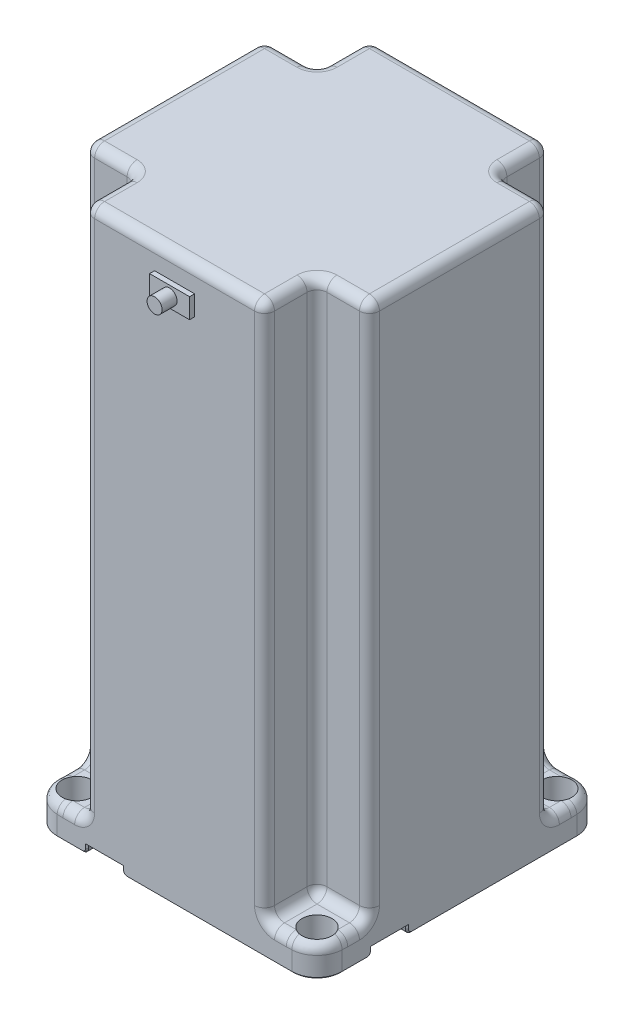
SolidWorks part; units mm, degrees
ref_plane "Płaszczyzna przednia" through (0, 0, 0) normal (0, 0, 1) x (1, 0, 0)
ref_plane "Płaszczyzna górna" through (0, 0, 0) normal (0, 1, 0) x (1, 0, 0)
ref_plane "Płaszczyzna prawa" through (0, 0, 0) normal (1, 0, 0) x (0, 0, -1)
sketch "Szkic1" plane through (0, 0, 0) normal (0, 1, 0) x (1, 0, 0)
  line L1 (28.5, -28.5) -> (-28.5, -28.5)
  line L2 (28.5, -28.5) -> (28.5, 28.5)
  line L3 (28.5, 28.5) -> (-28.5, 28.5)
  line L4 (-28.5, -28.5) -> (-28.5, 28.5)
  line L5 (28.5, -28.5) -> (-28.5, 28.5) construction
  line L6 (28.5, 28.5) -> (-28.5, -28.5) construction
  point P0 (0, 0)
  dimension "D1" = 57
  dimension "D2" = 57
extrude "Dodanie-wyciągnięcie1" add sketch "Szkic1" along normal blind 113
fillet "Zaokrąglenie1" radius 5 4 edges at (-28.5, 56.5, 28.5) (-28.5, 56.5, -28.5) (28.5, 56.5, -28.5) (28.5, 56.5, 28.5)
sketch "Szkic2" plane through (0, 113, 0) normal (0, 1, 0) x (1, 0, 0)
  line L0 (0, -31.35) -> (0, 31.35) construction
  line L1 (-30, -30) -> (30, -30)
  line L2 (-30, -30) -> (-30, 30)
  line L3 (-30, 30) -> (30, 30)
  line L6 (30, -30) -> (30, 30)
  line L7 (-30, -30) -> (30, 30) construction
  line L8 (-30, 30) -> (30, -30) construction
  line L9 (-31.35, 0) -> (31.35, 0) construction
  circle A0 centre (24, 24) radius 3
  circle A1 centre (24, -24) radius 3
  circle A2 centre (-24, -24) radius 3
  circle A4 centre (-24, 24) radius 3
  point P0 (0, 0)
  dimension "D2" = 6
  dimension "D1" = 60
  dimension "D3" = 60
  dimension "D4" = 6
  dimension "D5" = 6
extrude "Wytnij-wyciągnięcie1" cut sketch "Szkic2" against normal blind 113 contours A2 | A4 | A1 | A0 region at (-24, 113, 24)
sketch "Szkic3" plane through (0, 113, 0) normal (0, 1, 0) x (1, 0, 0)
  line L1 (-29.0454, 18) -> (-18, 18)
  line L2 (-29.0454, 18) -> (-29.0454, 29.0454)
  line L3 (-29.0454, 29.0454) -> (-18, 29.0454)
  line L4 (-18, 18) -> (-18, 29.0454)
  line L5 (-29.0454, 18) -> (-18, 29.0454) construction
  line L6 (-29.0454, 29.0454) -> (-18, 18) construction
  line L7 (0, -31.35) -> (0, 31.35) construction
  line L8 (29.0454, 29.0454) -> (18, 29.0454)
  line L9 (18, 18) -> (18, 29.0454)
  line L10 (29.0454, 18) -> (18, 18)
  line L11 (29.0454, 18) -> (29.0454, 29.0454)
  line L12 (-31.35, 0) -> (31.35, 0) construction
  line L13 (29.0454, -18) -> (29.0454, -29.0454)
  line L14 (29.0454, -18) -> (18, -18)
  line L15 (18, -18) -> (18, -29.0454)
  line L16 (29.0454, -29.0454) -> (18, -29.0454)
  line L17 (-29.0454, -29.0454) -> (-18, -29.0454)
  line L18 (-18, -18) -> (-18, -29.0454)
  line L19 (-29.0454, -18) -> (-18, -18)
  line L20 (-29.0454, -18) -> (-29.0454, -29.0454)
  circle A0 centre (-24, 24) radius 3 construction
  point P0 (-24, 24)
  dimension "D1" = 6
  dimension "D2" = 6
  dimension "D3" = 11.0454
extrude "Wytnij-wyciągnięcie2" cut sketch "Szkic3" against normal blind 107
fillet "Zaokrąglenie2" radius 2 41 edges at (-28.5, 6, -20.75) (-20.75, 6, -28.5) (28.5, 6, -20.75) (20.75, 6, -28.5) (28.5, 6, 20.75) (20.75, 6, 28.5) (-18, 59.5, 28.5) (-28.5, 6, 20.75) (-28.5, 113, 0) (0, 113, -28.5) (28.5, 113, 0) (0, 113, 28.5) (-18, 113, 23.25) (-28.5, 59.5, -18) (-23.25, 6, -18) (-23.25, 113, -18) (-18, 59.5, -18) (-18, 6, -23.25) (-18, 59.5, -28.5) (-18, 113, -23.25) (28.5, 59.5, -18) (23.25, 113, -18) (23.25, 6, -18) (18, 59.5, -28.5) (18, 6, -23.25) (18, 59.5, -18) (18, 113, -23.25) (28.5, 59.5, 18) (23.25, 6, 18) (23.25, 113, 18) (18, 59.5, 18) (18, 6, 23.25) (18, 59.5, 28.5) (18, 113, 23.25) (-28.5, 59.5, 18) (-23.25, 113, 18) (-18, 59.5, 18) (-23.25, 6, 18) (-18, 6, 23.25) (-20.75, 6, 28.5) (-27.0355, 6, 27.0355)
sketch "Szkic5" plane through (0, 0, 0) normal (0, -1, 0) x (1, 0, 0)
  circle A0 centre (0, 0) radius 19
  dimension "D1" = 38
extrude "Dodanie-wyciągnięcie2" add sketch "Szkic5" along normal blind 0.9
fillet "Zaokrąglenie8" radius 1 1 edges at (0, -0.9, -19)
sketch "Szkic6" plane through (0, -0.9, 0) normal (0, -1, 0) x (-1, 0, 0)
  circle A0 centre (0, 0) radius 5
  dimension "D1" = 10
extrude "Wytnij-wyciągnięcie4" cut sketch "Szkic6" against normal blind 50
sketch "Szkic7" plane through (0, 0, 0) normal (0, -1, 0) x (1, 0, 0)
  line L0 (-23.5, 28.5) -> (23.5, 28.5) construction
  circle A0 centre (-14, 23.5) radius 2
  circle A1 centre (23.5, 14) radius 2
  circle A2 centre (14, -23.5) radius 2
  circle A3 centre (-23.5, -14) radius 2
  circle A4 centre (0, 0) radius 5 construction
  circle A6 centre (-24, 24) radius 3 construction
  point P15 (0, 0)
  dimension "D1" = 4
  dimension "D2" = 10
  dimension "D4" = 5
  dimension "D3" = 4
extrude "Wytnij-wyciągnięcie5" cut sketch "Szkic7" against normal blind 100
sketch "Szkic8" plane through (0, 0, 0) normal (0, -1, 0) x (1, 0, 0)
  line L0 (-17.5, 23.5) -> (-17.5, 28.5)
  line L1 (-23.5, 28.5) -> (23.5, 28.5) construction
  line L2 (-17.5, 28.5) -> (-10.5, 28.5)
  line L3 (-10.5, 28.5) -> (-10.5, 23.5)
  line L4 (-28.5, -23.5) -> (-28.5, 23.5) construction
  arc A0 (-17.5, 23.5) -> (-10.5, 23.5) centre (-14, 23.5) ccw
  point P3 (-14, 28.5)
  dimension "D1" = 3.5
  dimension "D2" = 14.5
  dimension "D3" = 5
extrude "Wytnij-wyciągnięcie6" cut sketch "Szkic8" against normal blind 1.5
fillet "Zaokrąglenie9" radius 1 3 edges at (-17.5, 0, 26) (-10.5, 0, 26) (-14, 0, 20)
pattern_circular "Szyk kołowy3" count 4 over 360 about axis through (0, 49.1, 0) along (0, -1, 0) of "Wytnij-wyciągnięcie6", "Zaokrąglenie9" reverse direction yes
chamfer "Sfazowanie1" distance 0.3 angle 45 36 edges at (-23.5, 1.5, -16) (14, 1.5, -25.5) (23.5, 1.5, 12) (-14, 1.5, 21.5) (-28.5, 1.5, -14) (-14, 1.5, 28.5) (28.5, 1.5, 14) (28.5, 1.25, 10.5) (28.5, 0.2929, 10.2071) (28.5, 0, -7) (17.5, 1.25, -28.5) (27.0355, 0, -27.0355) (17.7929, 0.2929, -28.5) (21, 0, -28.5) (14, 1.5, -28.5) (-28.5, 1.25, -17.5) (-28.5, 0.2929, -17.7929) (10.5, 1.25, -28.5) (-28.5, 0, -21) (10.2071, 0.2929, -28.5) (-27.0355, 0, -27.0355) (-7, 0, -28.5) (-28.5, 1.25, -10.5) (-28.5, 0.2929, -10.2071) (-28.5, 0, 7) (-17.5, 1.25, 28.5) (-27.0355, 0, 27.0355) (-17.7929, 0.2929, 28.5) (-21, 0, 28.5) (28.5, 1.25, 17.5) (28.5, 0.2929, 17.7929) (-10.5, 1.25, 28.5) (28.5, 0, 21) (-10.2071, 0.2929, 28.5) (27.0355, 0, 27.0355) (7, 0, 28.5)
sketch "Szkic9" plane through (0, 0, 28.5) normal (0, 0, 1) x (1, 0, 0)
  line L0 (-16, 113) -> (16, 113) construction
  line L1 (4, 104) -> (-4, 104)
  line L2 (4, 104) -> (4, 108)
  line L3 (4, 108) -> (-4, 108)
  line L4 (-4, 104) -> (-4, 108)
  line L5 (4, 104) -> (-4, 108) construction
  line L6 (4, 108) -> (-4, 104) construction
  line L7 (16, 111) -> (-16, 111) construction
  point P0 (0, 106)
  point P10 (0, 111)
  dimension "D1" = 5
  dimension "D2" = 4
  dimension "D3" = 8
extrude "Dodanie-wyciągnięcie4" add sketch "Szkic9" along normal blind 1
sketch "Szkic10" plane through (0, 0, 29.5) normal (0, 0, 1) x (1, 0, 0)
  line L1 (4, 108) -> (-4, 108) construction
  line L3 (4, 104) -> (4, 108) construction
  circle A0 centre (0, 106) radius 1.5
  point P5 (4, 106)
  point P8 (0, 108)
  dimension "D1" = 3
extrude "Dodanie-wyciągnięcie5" add sketch "Szkic10" along normal blind 3
